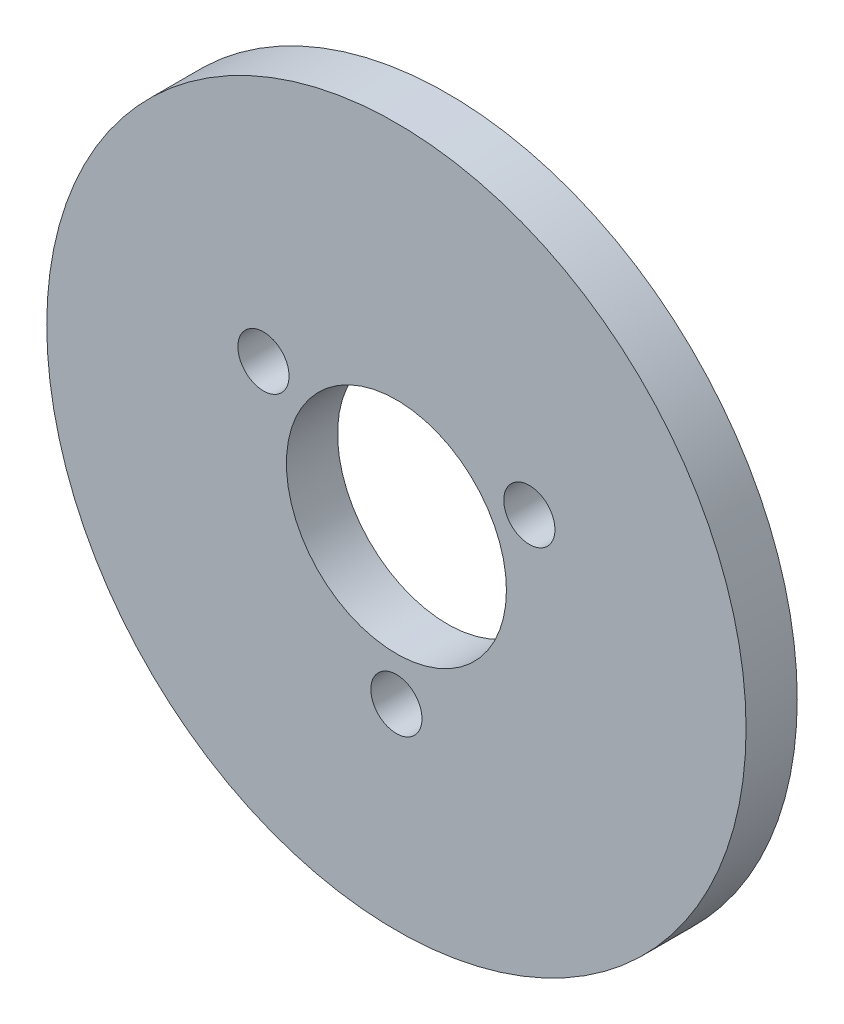
SolidWorks part; units mm, degrees
material "Acrylic (Medium-high impact)"
ref_plane "Front Plane" through (0, 0, 0) normal (0, 0, 1) x (1, 0, 0)
ref_plane "Top Plane" through (0, 0, 0) normal (0, 1, 0) x (1, 0, 0)
ref_plane "Right Plane" through (0, 0, 0) normal (1, 0, 0) x (0, 0, -1)
sketch "Sketch1" plane through (0, 0, 0) normal (0, 0, 1) x (1, 0, 0)
  circle A0 centre (0, 0) radius 20.5
  circle A1 centre (0, 0) radius 6.45
  dimension "D1" = 41
  dimension "D2" = 12.9
extrude "Boss-Extrude1" add sketch "Sketch1" along normal blind 3
sketch "Sketch2" plane through (0, 0, 0) normal (0, 0, -1) x (-1, 0, 0)
  circle A1 centre (7.7942, 4.5) radius 1.5
  circle A2 centre (7.7942, 4.5) radius 1.5
  circle A3 centre (-7.7942, 4.5) radius 1.5
  circle A4 centre (-7.7942, 4.5) radius 1.5
  circle A5 centre (0, -9) radius 1.5
  circle A6 centre (0, -9) radius 1.5
  dimension "D1" = 0
  dimension "D2" = 0
  dimension "D3" = 0
extrude "Cut-Extrude1" cut sketch "Sketch2" against normal through all
equation "\"smallPulleyTeeth\"= 30"
equation "\"largePulleyTeeth\"= 30"
equation "\"eighthThick\"= 3.0mm"
equation "\"sixteenthThick\"= 1.7mm"
equation "\"quarterThick\"=6.0mm"
equation "\"D1@Boss-Extrude1\"=\"eighthThick\""
